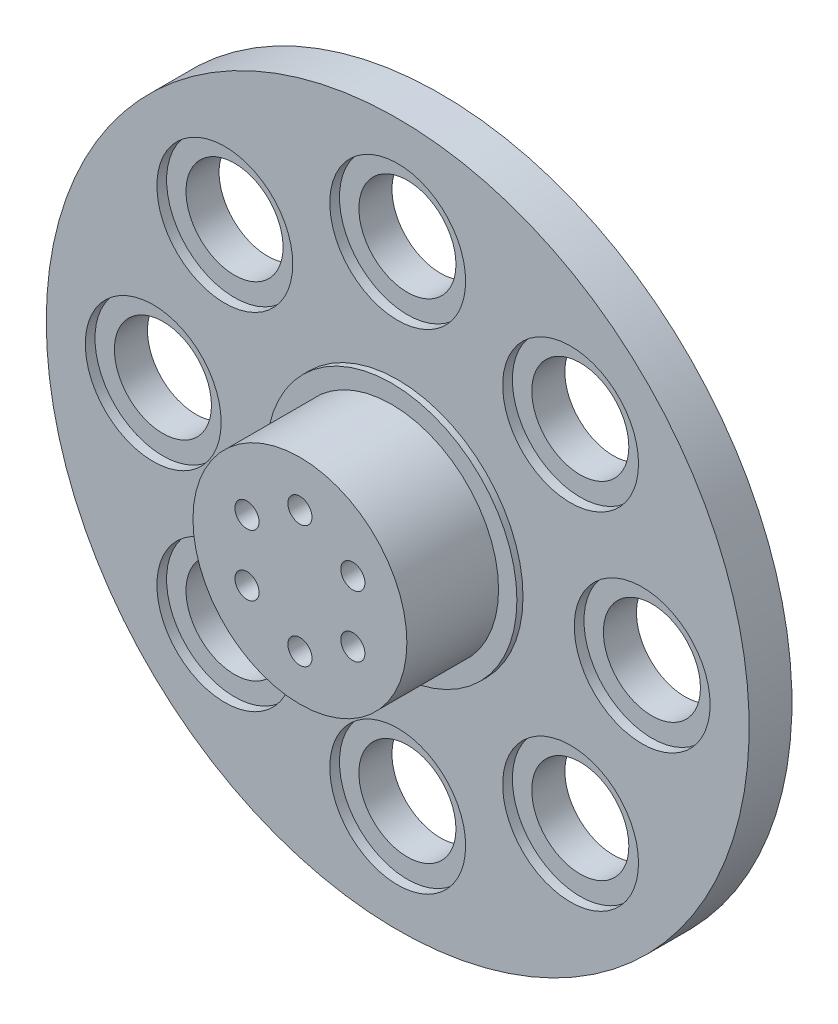
SolidWorks part; units mm, degrees
material "PETG"
ref_plane "Front Plane" through (0, 0, 0) normal (0, 0, 1) x (1, 0, 0)
ref_plane "Top Plane" through (0, 0, 0) normal (0, 1, 0) x (1, 0, 0)
ref_plane "Right Plane" through (0, 0, 0) normal (1, 0, 0) x (0, 0, -1)
sketch "Sketch1" plane through (0, 0, 0) normal (0, 0, 1) x (1, 0, 0)
  circle A0 centre (0, 0) radius 17.5
  dimension "D1" = 35
extrude "Boss-Extrude1" add sketch "Sketch1" along normal blind 15
sketch "Sketch7" plane through (0, 0, 0) normal (0, 0, -1) x (-1, 0, 0)
  circle A0 centre (0, 0) radius 20.5
  dimension "D1" = 41
extrude "Boss-Extrude3" add sketch "Sketch7" along normal blind 1
sketch "Sketch3" plane through (0, 0, -1) normal (0, 0, -1) x (-1, 0, 0)
  circle A0 centre (0, 0) radius 57.5
  dimension "D1" = 115
extrude "Boss-Extrude2" add sketch "Sketch3" along normal blind 7
sketch "Sketch4" plane through (0, 0, -8) normal (0, 0, -1) x (-1, 0, 0)
  circle A0 centre (0, 0) radius 11
  dimension "D1" = 22
extrude "Cut-Extrude1" cut sketch "Sketch4" against normal blind 7
sketch "Sketch5" plane through (0, 0, -1) normal (0, 0, -1) x (-1, 0, 0)
  circle A0 centre (0, 0) radius 7.5
  dimension "D1" = 15
extrude "Cut-Extrude2" cut sketch "Sketch5" against normal blind 0.5
sketch "Sketch6" plane through (0, 0, 15) normal (0, 0, 1) x (1, 0, 0)
  circle A0 centre (0, 10) radius 1.975
  dimension "D1" = 3.95
  dimension "D2" = 10
extrude "Cut-Extrude3" cut sketch "Sketch6" against normal blind 6
pattern_circular "CirPattern1" count 6 over 360 about axis through (0, 0, 15) along (0, 0, 1) of "Cut-Extrude3"
sketch "Sketch8" plane through (0, 0, -1) normal (0, 0, 1) x (1, 0, 0)
  circle A0 centre (0, 0) radius 40 construction
  circle A1 centre (-40, 0) radius 7.94
  circle A2 centre (-28.2843, 28.2843) radius 7.94
  circle A3 centre (0, 40) radius 7.94
  circle A4 centre (28.2843, 28.2843) radius 7.94
  circle A5 centre (40, 0) radius 7.94
  circle A6 centre (28.2843, -28.2843) radius 7.94
  circle A7 centre (0, -40) radius 7.94
  circle A8 centre (-28.2843, -28.2843) radius 7.94
  dimension "D1" = 80
  dimension "D2" = 15.88
  dimension "D3" = 8
extrude "Cut-Extrude4" cut sketch "Sketch8" against normal through all
sketch "Sketch9" plane through (0, 0, -1) normal (0, 0, 1) x (1, 0, 0)
  line L0 (0, 0) -> (0, 40) construction
  circle A0 centre (0, 40) radius 11.1125
  circle A1 centre (0, 40) radius 7.94 construction
  circle A2 centre (28.2843, 28.2843) radius 11.1125
  circle A3 centre (40, 0) radius 11.1125
  circle A4 centre (28.2843, -28.2843) radius 11.1125
  circle A5 centre (0, -40) radius 11.1125
  circle A6 centre (-28.2843, -28.2843) radius 11.1125
  circle A7 centre (-40, 0) radius 11.1125
  circle A8 centre (-28.2843, 28.2843) radius 11.1125
  point P17 (0, 0)
  dimension "D1" = 22.225
  dimension "D2" = 8
extrude "Cut-Extrude5" cut sketch "Sketch9" against normal blind 1.5875
equation "\"N\"= 21"
equation "\"R\"= 65mm"
equation "\"E\" = ROUND(\"R\" / \"N\" * 0.7, 2)"
equation "\"R_r\" = ( 1in / 2 ) / 2"
equation "\"D_p\" = 8cm"
equation "\"D1@Sketch8\"=\"D_p\""
equation "\"N_p\"= 8"
equation "\"D3@Sketch8\"=\"N_p\""
